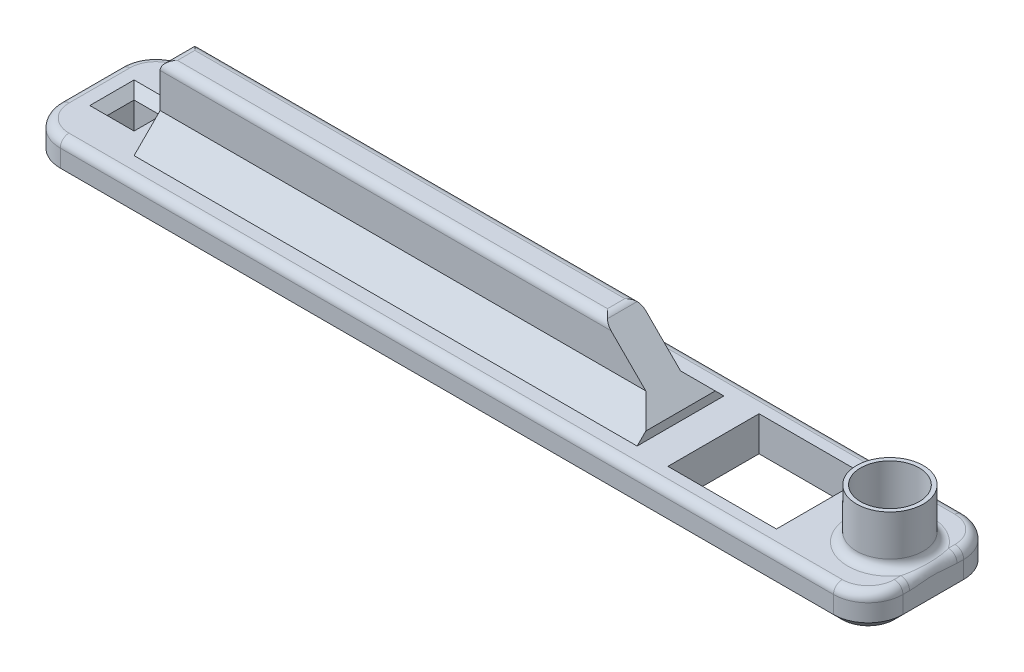
SolidWorks part; units mm, degrees
ref_plane "Front Plane" through (0, 0, 0) normal (0, 0, 1) x (1, 0, 0)
ref_plane "Top Plane" through (0, 0, 0) normal (0, 1, 0) x (1, 0, 0)
ref_plane "Right Plane" through (0, 0, 0) normal (1, 0, 0) x (0, 0, -1)
sketch "Sketch1" plane through (0, 0, 0) normal (0, 1, 0) x (1, 0, 0)
  line L1 (0, 0) -> (97.07, 0)
  line L2 (0, 0) -> (0, 15)
  line L3 (0, 15) -> (97.07, 15)
  line L4 (97.07, 0) -> (97.07, 15)
  dimension "D1" = 97.07
  dimension "D2" = 15
extrude "Boss-Extrude1" add sketch "Sketch1" along normal blind 4
sketch "Sketch2" plane through (0, 4, 0) normal (0, 1, 0) x (1, 0, 0)
  line L0 (0, 15) -> (0, 0) construction
  line L1 (0, 5.5) -> (67.949, 5.5)
  line L2 (0, 5.5) -> (0, 9.5)
  line L3 (0, 9.5) -> (67.949, 9.5)
  line L4 (67.949, 5.5) -> (67.949, 9.5)
  line L6 (0, 0) -> (97.07, 0) construction
  dimension "D2" = 5.5
  dimension "D3" = 67.949
extrude "Boss-Extrude2" add sketch "Sketch2" along normal blind 8
chamfer "Chamfer1" distance 7 angle 45 2 edges at (67.949, 12, -7.5) (0, 12, -7.5)
chamfer "Chamfer2" distance 3 angle 45 2 edges at (33.9745, 4, -9.5) (33.9745, 4, -5.5)
sketch "Sketch3" plane through (0, 0, 0) normal (0, -1, 0) x (1, 0, 0)
  line L0 (97.07, -15) -> (0, -15) construction
  line L1 (0, -15) -> (0, 0) construction
  line L2 (97.07, 0) -> (97.07, -15) construction
  line L4 (3.45, -9.05) -> (6.55, -9.05)
  line L5 (3.45, -9.05) -> (3.45, -5.95)
  line L6 (3.45, -5.95) -> (6.55, -5.95)
  line L7 (6.55, -9.05) -> (6.55, -5.95)
  line L8 (3.45, -9.05) -> (6.55, -5.95) construction
  line L9 (3.45, -5.95) -> (6.55, -9.05) construction
  circle A0 centre (5, -7.5) radius 1.55 construction
  circle A1 centre (92.07, -7.5) radius 2.05
  point P14 (5, -5.95)
  point P15 (6.55, -7.5)
  dimension "D1" = 3.1
  dimension "D2" = 4.1
  dimension "D3" = 7.5
  dimension "D4" = 7.5
  dimension "D5" = 5
  dimension "D6" = 5
extrude "Cut-Extrude1" cut sketch "Sketch3" against normal through all
sketch "Sketch6" plane through (0, 0, 0) normal (0, -1, 0) x (1, 0, 0)
  line L1 (97.07, -15) -> (0, -15) construction
  circle A0 centre (47.99, -7.5) radius 5.075
  circle A1 centre (92.07, -7.5) radius 2.05 construction
  dimension "D1" = 10.15
  dimension "D2" = 7.5
  dimension "D3" = 44.08
extrude "Cut-Extrude4" cut sketch "Sketch6" against normal blind 3
sketch "Sketch7" plane through (0, 4, 0) normal (0, 1, 0) x (1, 0, 0)
  line L0 (67.949, 2.5) -> (0, 2.5) construction
  line L1 (0, 12.5) -> (10, 12.5)
  line L2 (0, 12.5) -> (0, 2.5)
  line L3 (0, 2.5) -> (10, 2.5)
  line L4 (10, 12.5) -> (10, 2.5)
  dimension "D1" = 10
extrude "Cut-Extrude5" cut sketch "Sketch7" along normal through all
fillet "Fillet1" radius 1 4 edges at (35.4745, 12, -5.5) (35.4745, 12, -9.5) (10, 12, -7.5) (60.949, 12, -7.5)
fillet "Fillet3" radius 4 4 edges at (97.07, 2, 0) (0, 2, 0) (0, 2, -15) (97.07, 2, -15)
chamfer "Chamfer3" distance 0.5 angle 45 2 edges at (92.07, 0, -9.55) (47.99, 0, -12.575)
sketch "Sketch8" plane through (0, 0, 0) normal (0, -1, 0) x (-1, 0, 0)
  line L0 (-84.245, 12.75) -> (-71.745, 2.25) construction
  line L1 (-71.745, 12.75) -> (-84.245, 12.75)
  line L2 (-71.745, 12.75) -> (-71.745, 2.25)
  line L3 (-71.745, 2.25) -> (-84.245, 2.25)
  line L4 (-84.245, 12.75) -> (-84.245, 2.25)
  line L5 (-71.745, 12.75) -> (-84.245, 2.25) construction
  line L6 (-77.995, 7.5) -> (-92.07, 7.5) construction
  dimension "D2" = 10.5
  dimension "D3" = 12.5
  dimension "D1" = 14.075
extrude "Cut-Extrude7" cut sketch "Sketch8" against normal up to surface (12 mm away) up to face at (35.7674, 12, -7.5)
sketch "Sketch9" plane through (0, 4, 0) normal (0, 1, 0) x (1, 0, 0)
  circle A0 centre (92.07, 7.5) radius 3.375
  circle A1 centre (92.07, 7.5) radius 3.847
  dimension "D1" = 6.75
extrude "Boss-Extrude3" add sketch "Sketch9" along normal blind 5.7
fillet "Fillet4" radius 1 1 edges at (92.07, 4, -11.347)
sketch "Sketch10" plane through (0, 0, 0) normal (0, 0, 1) x (1, 0, 0)
  line L1 (40.087, 25.075) -> (50.087, 25.075) construction
  line L2 (40.087, 25.075) -> (40.087, 13.075) construction
  line L3 (40.087, 13.075) -> (50.087, 13.075) construction
  line L4 (50.087, 25.075) -> (50.087, 13.075) construction
  circle A0 centre (45.087, 42.435) radius 15.24 construction
  circle A1 centre (45.087, 19.075) radius 7.62 construction
  dimension "D1" = 30.48
  dimension "D2" = 15.24
  dimension "D3" = 23.36
  dimension "D4" = 12
  dimension "D5" = 10
  dimension "D7" = 6
  dimension "D8" = 5
ref_plane "Plane1" through (30, 0, 0) normal (-1, 0, 0) x (0, 0, 1)
sketch "Sketch11" plane through (30, 0, 0) normal (-1, 0, 0) x (0, 0, 1)
  line L0 (-15, 0) -> (0, 0)
  line L1 (-14, 0) -> (-1, 0)
  line L2 (-15, 0) -> (-15, 4)
  line L3 (-15, 1) -> (-15, 3)
  line L4 (0, 4) -> (0, 0)
  line L5 (0, 3) -> (0, 1)
  line L6 (-15, 4) -> (-12.5, 4)
  line L7 (-2.5, 4) -> (0, 4)
  line L8 (-2.5, 4) -> (-1, 4)
  line L9 (-14, 4) -> (-12.5, 4)
  line L10 (-5.5, 7) -> (-2.5, 4)
  line L11 (-5.5, 7) -> (-2.5, 4)
  line L12 (-5.5, 11) -> (-5.5, 7)
  line L13 (-5.5, 11) -> (-5.5, 7)
  line L14 (-8.5, 12) -> (-6.5, 12)
  line L15 (-8.5, 12) -> (-6.5, 12)
  line L16 (-9.5, 7) -> (-9.5, 11)
  line L17 (-9.5, 7) -> (-9.5, 11)
  line L18 (-12.5, 4) -> (-9.5, 7)
  line L19 (-12.5, 4) -> (-9.5, 7)
  arc A0 (0, 1) -> (-1, 0) centre (-1, 1) cw
  arc A2 (0, 3) -> (-1, 4) centre (-1, 3) ccw
  arc A4 (-14, 0) -> (-15, 1) centre (-14, 1) cw
  arc A6 (-5.5, 11) -> (-6.5, 12) centre (-6.5, 11) ccw
  arc A7 (-5.5, 11) -> (-6.5, 12) centre (-6.5, 11) ccw
  arc A8 (-8.5, 12) -> (-9.5, 11) centre (-8.5, 11) ccw
  arc A9 (-8.5, 12) -> (-9.5, 11) centre (-8.5, 11) ccw
  arc A10 (-14, 4) -> (-15, 3) centre (-14, 3) ccw
  dimension "D1" = 1
fillet "Fillet5" [suppressed] radius 4
fillet "Fillet6" radius 1 8 edges at (0, 4, -7.5) (48.535, 4, -15) (97.07, 4, -7.5) (48.535, 4, 0) (1.1716, 4, -1.1716) (1.1716, 4, -13.8284) (95.8984, 4, -13.8284) (95.8984, 4, -1.1716)
chamfer "Chamfer4" distance 1 angle 45 8 edges at (48.535, 0, -15) (0, 0, -7.5) (97.07, 0, -7.5) (48.535, 0, 0) (1.1716, 0, -13.8284) (95.8984, 0, -13.8284) (1.1716, 0, -1.1716) (95.8984, 0, -1.1716)
chamfer "Chamfer5" distance 1 angle 45 4 edges at (5, 4, -9.05) (6.55, 4, -7.5) (3.45, 4, -7.5) (5, 4, -5.95)
equation "\"D1@Sketch9\"=0.27*25"
equation "\"D3@Sketch2\"=\"D1@Sketch1\"*70/100"
equation "\"D1@Sketch1\"=93-2.57+6.64"
equation "\"D1@Sketch8\"=11+3.075"
